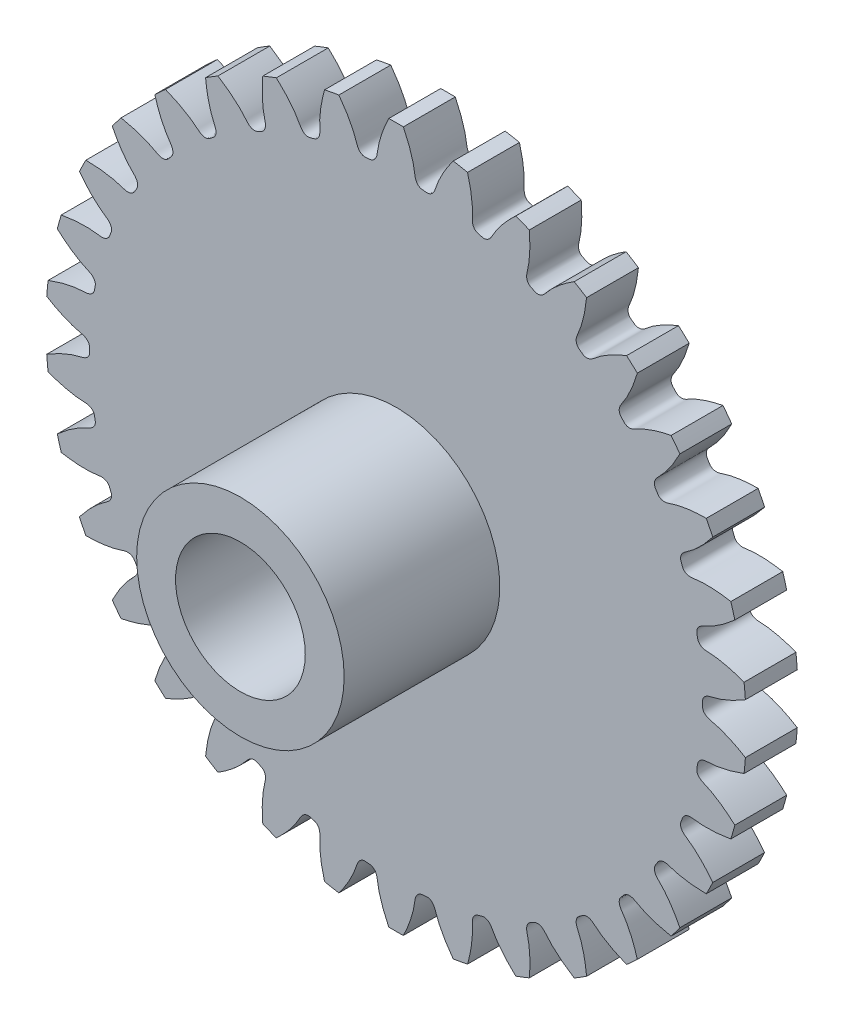
SolidWorks part; units mm, degrees
ref_plane "Alzado" through (0, 0, 0) normal (0, 0, 1) x (1, 0, 0)
ref_plane "Planta" through (0, 0, 0) normal (0, 1, 0) x (1, 0, 0)
ref_plane "Vista lateral" through (0, 0, 0) normal (1, 0, 0) x (0, 0, -1)
ref_axis "Eje1" through (0, 0, 55) along (0, 0, -1)
sketch "SketchRevolveSpur02" plane through (0, 0, 0) normal (1, 0, 0) x (0, 0, -1)
  line L0 (0, 0) -> (1, 0) construction
  line L1 (-0.25, 0) -> (-0.25, 3.375)
  line L2 (-0.25, 3.375) -> (0.25, 3.375)
  line L3 (0.25, 3.375) -> (0.25, 0)
  line L4 (0.25, 0) -> (-0.25, 0)
revolve "Spur02" add sketch "SketchRevolveSpur02" angle 360 about L0
sketch "SketchToothSpur02" plane through (0, 0, 0) normal (0, 0, 1) x (1, 0, 0)
  arc A0 (3.3753, 0.2471) -> (3.3753, -0.2471) centre (0, 0) cw
  spline S0 degree 3 poles (3.3753, -0.2471) (3.3473, -0.2296) (3.3101, -0.208) (3.2635, -0.1838) (3.2379, -0.1712) (3.2134, -0.1598) (3.19, -0.1496) (3.1678, -0.1405) (3.1468, -0.1324) (3.127, -0.1253) (3.1085, -0.1191) (3.0913, -0.1138) (3.0755, -0.1092) (3.0589, -0.1049) (3.0457, -0.1017) (3.0353, -0.0997) (3.0296, -0.0984) (3.0241, -0.0969) (3.0187, -0.0954) (3.0134, -0.0936) (3.0082, -0.0917) (3.0031, -0.0895) (2.998, -0.0872) (2.993, -0.0845) (2.988, -0.0815) (2.983, -0.078) (2.9779, -0.0739) (2.9729, -0.0692) (2.968, -0.0635) (2.9632, -0.0569) (2.959, -0.049) (2.9556, -0.04) (2.9535, -0.0304) (2.9527, -0.017) (2.9534, 0) (2.9527, 0.017) (2.9535, 0.0304) (2.9556, 0.04) (2.959, 0.049) (2.9632, 0.0569) (2.968, 0.0635) (2.9729, 0.0692) (2.9779, 0.0739) (2.983, 0.078) (2.988, 0.0815) (2.993, 0.0845) (2.998, 0.0872) (3.0031, 0.0895) (3.0082, 0.0917) (3.0134, 0.0936) (3.0187, 0.0954) (3.0241, 0.0969) (3.0296, 0.0984) (3.0353, 0.0997) (3.0457, 0.1017) (3.0589, 0.1049) (3.0755, 0.1092) (3.0913, 0.1138) (3.1085, 0.1191) (3.127, 0.1253) (3.1468, 0.1324) (3.1678, 0.1405) (3.19, 0.1496) (3.2134, 0.1598) (3.2379, 0.1712) (3.2635, 0.1838) (3.3101, 0.208) (3.3473, 0.2296) (3.3753, 0.2471) knots 0 0 0 0 0.095745 0.12476 0.152324 0.178438 0.203101 0.226314 0.248076 0.268387 0.287248 0.304658 0.320618 0.335127 0.354354 0.360112 0.365745 0.37127 0.376705 0.382076 0.38741 0.392744 0.398121 0.403594 0.409228 0.415102 0.42131 0.427958 0.435163 0.443033 0.45164 0.460982 0.470942 0.479784 0.5 0.520216 0.529058 0.539018 0.54836 0.556967 0.564837 0.572042 0.57869 0.584898 0.590772 0.596406 0.601879 0.607256 0.61259 0.617924 0.623295 0.62873 0.634255 0.639888 0.645646 0.664873 0.679382 0.695342 0.712752 0.731613 0.751924 0.773686 0.796899 0.821562 0.847676 0.87524 0.904255 1 1 1 1
extrude "ToothExtrudeCutSpur02" cut sketch "SketchToothSpur02" against normal blind 0.25 and the other way blind 0.25
pattern_circular "PatternSpur02" count 34 every 10.588 about axis through (0, 0, 55) along (0, 0, -1) of "ToothExtrudeCutSpur02"
sketch "AuxiliarySketchSpur02" plane through (0, 0, 0) normal (0, 0, 1) x (1, 0, 0)
  circle A0 centre (0, 0) radius 3.1875 construction
  circle A1 centre (0, 0) radius 2.9953 construction
  circle A2 centre (0, 0) radius 3.0389 construction
  circle A3 centre (0, 0) radius 3.375 construction
  circle A4 centre (0, 0) radius 2.9531 construction
  dimension "PitchDiameter" = 6.375
  dimension "BaseDiameter" = 5.9905
  dimension "FormDiameter" = 6.0778
  dimension "MajorDiameter" = 6.75
  dimension "MinorDiameter" = 5.9062
sketch "Croquis5" plane through (0, 0, 0.25) normal (0, 0, 1) x (1, 0, 0)
  circle A0 centre (0, 0) radius 1
  dimension "D1" = 2
extrude "Saliente-Extruir1" add sketch "Croquis5" along normal blind 1.5
sketch "Croquis6" plane through (0, 0, 1.75) normal (0, 0, 1) x (1, 0, 0)
  circle A0 centre (0, 0) radius 0.625
  dimension "D1" = 1.25
extrude "Cortar-Extruir2" cut sketch "Croquis6" against normal up to next
